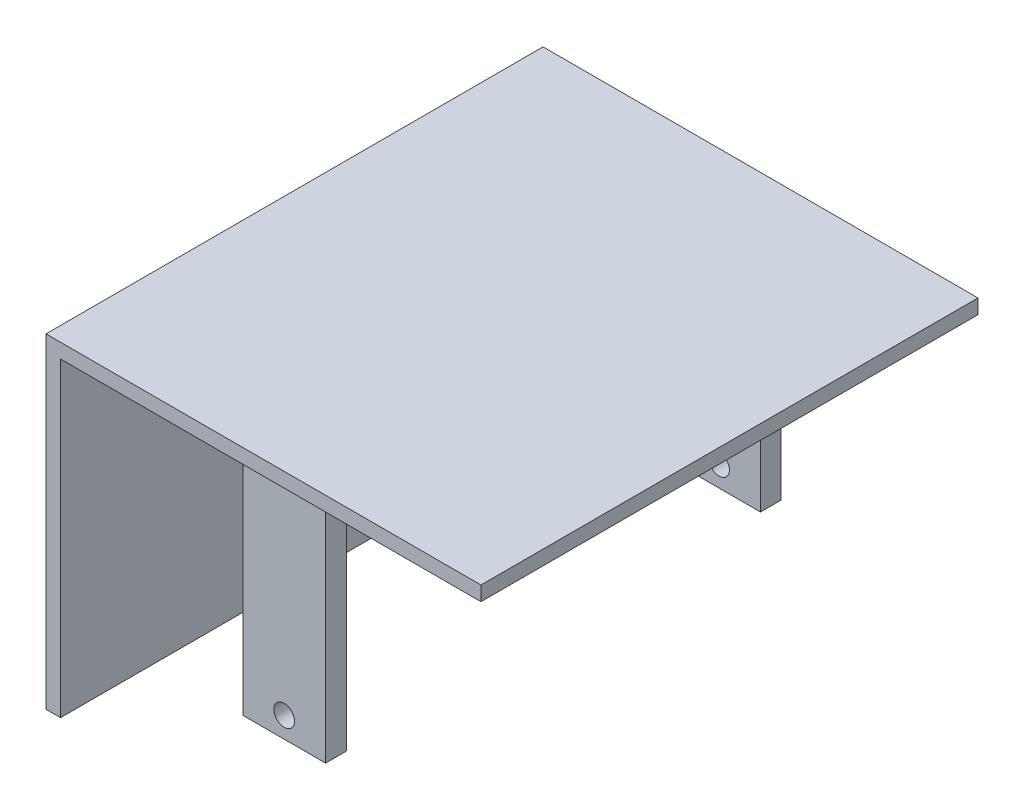
SolidWorks part; units mm, degrees
ref_plane "Front Plane" through (0, 0, 0) normal (0, 0, 1) x (1, 0, 0)
ref_plane "Top Plane" through (0, 0, 0) normal (0, 1, 0) x (1, 0, 0)
ref_plane "Right Plane" through (0, 0, 0) normal (1, 0, 0) x (0, 0, -1)
sketch "Sketch2" plane through (0, 0, 0) normal (0, 1, 0) x (1, 0, 0)
  line L0 (-248.92, 304.8) -> (-248.92, -304.8) construction
  line L1 (-266.7, 304.8) -> (266.7, 304.8)
  line L2 (-266.7, 304.8) -> (-266.7, -304.8)
  line L3 (-266.7, -304.8) -> (266.7, -304.8)
  line L4 (266.7, 304.8) -> (266.7, -304.8)
  line L5 (-266.7, 304.8) -> (266.7, -304.8) construction
  line L6 (-266.7, -304.8) -> (266.7, 304.8) construction
  line L8 (-50.8, -254) -> (50.8, -254)
  line L9 (-50.8, -254) -> (-50.8, -279.4)
  line L10 (-50.8, -279.4) -> (50.8, -279.4)
  line L11 (50.8, -254) -> (50.8, -279.4)
  line L12 (-50.8, -254) -> (50.8, -279.4) construction
  line L13 (-50.8, -279.4) -> (50.8, -254) construction
  line L14 (-50.8, 279.4) -> (50.8, 279.4)
  line L15 (-50.8, 279.4) -> (-50.8, 254)
  line L16 (-50.8, 254) -> (50.8, 254)
  line L17 (50.8, 279.4) -> (50.8, 254)
  line L18 (-50.8, 279.4) -> (50.8, 254) construction
  line L19 (-50.8, 254) -> (50.8, 279.4) construction
  point P0 (0, 0)
  point P8 (0, -266.7)
  point P13 (0, 266.7)
  point P21 (0, 304.8)
  dimension "D1" = 609.6
  dimension "D2" = 533.4
  dimension "D3" = 17.78
  dimension "D4" = 25.4
  dimension "D5" = 101.6
  dimension "D6" = 25.4
  dimension "D7" = 101.6
  dimension "D8" = 25.4
  dimension "D9" = 25.4
extrude "Boss-Extrude1" add sketch "Sketch2" along normal blind 17.78
sketch "Sketch3" plane through (0, 0, 0) normal (0, 1, 0) x (1, 0, 0)
  line L0 (50.8, -279.4) -> (50.8, -254) construction
  line L1 (50.8, -254) -> (-50.8, -254) construction
  line L2 (-50.8, -254) -> (-50.8, -279.4) construction
  line L3 (-50.8, -279.4) -> (50.8, -279.4) construction
  line L4 (50.8, -279.4) -> (50.8, -254)
  line L5 (50.8, -254) -> (-50.8, -254)
  line L6 (-50.8, -254) -> (-50.8, -279.4)
  line L7 (-50.8, -279.4) -> (50.8, -279.4)
  line L8 (50.8, 254) -> (50.8, 279.4) construction
  line L9 (50.8, 279.4) -> (-50.8, 279.4) construction
  line L10 (-50.8, 279.4) -> (-50.8, 254) construction
  line L11 (-50.8, 254) -> (50.8, 254) construction
  line L12 (50.8, 254) -> (50.8, 279.4)
  line L13 (50.8, 279.4) -> (-50.8, 279.4)
  line L14 (-50.8, 279.4) -> (-50.8, 254)
  line L15 (-50.8, 254) -> (50.8, 254)
extrude "Boss-Extrude2" add sketch "Sketch3" along normal blind 17.78
extrude "Boss-Extrude3" add sketch "Sketch3<2>" against normal blind 292.1
sketch "Sketch3<2>" plane through (0, 0, 0) normal (0, 1, 0) x (1, 0, 0) same geometry as "Sketch3"
sketch "Sketch4" plane through (0, 0, 0) normal (0, 0, 1) x (1, 0, 0)
  line L0 (0, 0) -> (0, -292.1) construction
  line L1 (-50.8, -292.1) -> (50.8, -292.1) construction
  line L3 (-266.7, 0) -> (266.7, 0) construction
  circle A0 centre (0, -266.7) radius 12.7
  dimension "D1" = 25.4
  dimension "D2" = 266.7
extrude "Cut-Extrude1" cut sketch "Sketch4" against normal blind 508 and the other way blind 508
sketch "Sketch5" plane through (0, 0, 0) normal (0, 1, 0) x (1, 0, 0)
  line L0 (-248.92, 304.8) -> (-248.92, -304.8) construction
  line L1 (-248.92, 304.8) -> (-248.92, -304.8)
  line L2 (-266.7, 304.8) -> (-266.7, -304.8) construction
  line L3 (-266.7, 304.8) -> (-266.7, -304.8)
  line L4 (-266.7, 304.8) -> (-248.92, 304.8)
  line L5 (-248.92, -304.8) -> (-266.7, -304.8)
extrude "Boss-Extrude4" add sketch "Sketch5" against normal blind 381
